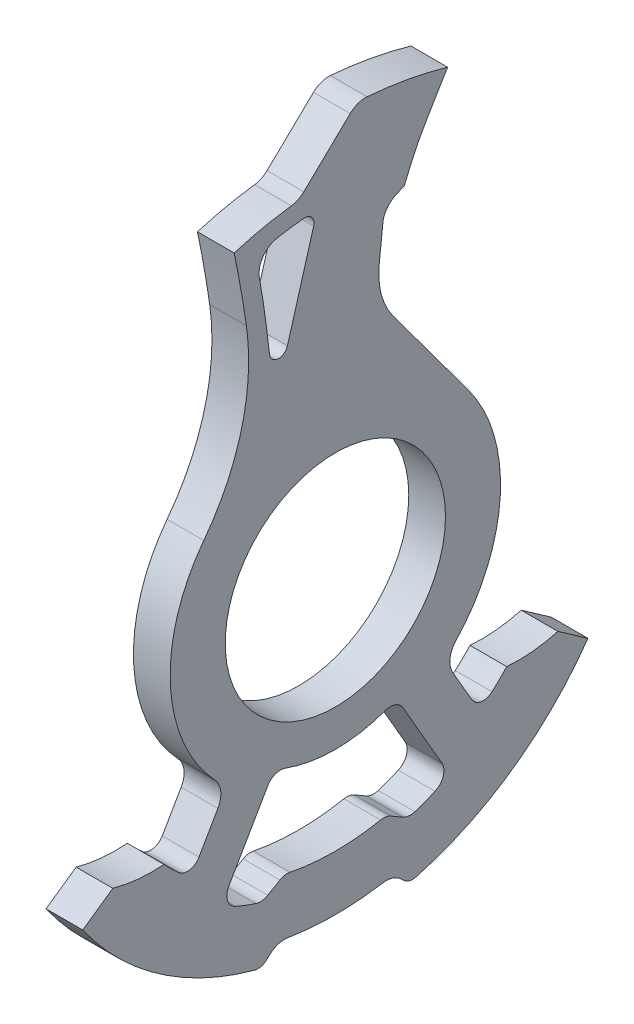
SolidWorks part; units mm, degrees
material "AR500"
ref_plane "Front Plane" through (0, 0, 0) normal (0, 0, 1) x (1, 0, 0)
ref_plane "Top Plane" through (0, 0, 0) normal (0, 1, 0) x (1, 0, 0)
ref_plane "Right Plane" through (0, 0, 0) normal (1, 0, 0) x (0, 0, -1)
other "Center of Mass"
sketch "Sketch1" plane through (0, 0, 0) normal (1, 0, 0) x (0, 0, -1)
  circle A0 centre (0, 0) radius 139.7 construction
  circle A1 centre (0, 0) radius 106.68 construction
  circle A2 centre (0, 0) radius 38.1 construction
  dimension "D1" = 279.4
  dimension "D2" = 33.02
  dimension "D3" = 76.2
sketch "Sketch2" plane through (0, 0, 0) normal (1, 0, 0) x (0, 0, -1)
  line L0 (0, 0) -> (38.858, 134.187) construction
  line L1 (38.858, 134.187) -> (32.2885, 123.3181)
  line L2 (0, 0) -> (0, 61.679) construction
  line L3 (7.5549, 139.4956) -> (-12.768, 119.9725)
  line L4 (-35.0051, 115.4602) -> (-40.3483, 140.8902) construction
  line L5 (23.88, 106.192) -> (20.1469, 96.5425) construction
  line L6 (23.88, 106.192) -> (16.9106, 103.1109)
  line L7 (16.9106, 103.1109) -> (15.1624, 86.8858)
  line L8 (-35.0051, 115.4602) -> (-4.6687, 124.6576) construction
  line L10 (0, -100.33) -> (0, 0) construction
  line L11 (-20.0866, -98.2987) -> (-25.4, -103.6121)
  line L16 (-49.9001, -64.1593) -> (-37.6706, -42.9773)
  line L17 (87.3871, -61.1891) -> (76.9839, -53.9047)
  line L18 (-87.3871, -61.1891) -> (-76.9839, -53.9047)
  line L19 (49.9001, -64.1593) -> (37.6706, -42.9773)
  line L24 (53.8815, -53.8815) -> (0, 0) construction
  line L25 (20.0866, -98.2987) -> (25.4, -103.6121)
  line L26 (19.9976, 69.057) -> (45.9419, 33.9922)
  circle A0 centre (0, 0) radius 139.7 construction
  arc A1 (38.858, 134.187) -> (7.5549, 139.4956) centre (0, 0) ccw
  arc A2 (-12.768, 119.9725) -> (-35.0051, 115.4602) centre (0, 0) ccw
  arc A3 (32.2885, 123.3181) -> (23.88, 106.192) centre (125.9607, 66.6999) ccw
  arc A4 (45.9419, 33.9922) -> (37.6706, -42.9773) centre (0, 0) cw
  circle A5 centre (0, 0) radius 38.1 construction
  arc A6 (19.9976, 69.057) -> (15.1624, 86.8858) centre (40.4162, 84.1646) cw
  arc A7 (-35.0051, 115.4602) -> (-30.7712, 91.5455) centre (-407.8633, 37.1165) cw
  arc A8 (-30.7712, 91.5455) -> (-45.5098, 34.5685) centre (-106.1896, 80.6597) cw
  arc A9 (-45.5098, 34.5685) -> (-37.6706, -42.9773) centre (0, 0) ccw
  arc A10 (-87.3871, -61.1891) -> (-25.4, -103.6121) centre (0, 0) ccw
  circle A11 centre (0, 0) radius 106.68 construction
  arc A18 (-76.9839, -53.9047) -> (-59.2852, -55.6031) centre (-63.357, -4.9665) ccw
  arc A19 (-59.2852, -55.6031) -> (-49.9001, -64.1593) centre (0, 0) ccw
  arc A20 (-20.0866, -98.2987) -> (20.0866, -98.2987) centre (0, 0) ccw
  arc A21 (59.2852, -55.6031) -> (49.9001, -64.1593) centre (0, 0) cw
  arc A22 (76.9839, -53.9047) -> (59.2852, -55.6031) centre (63.357, -4.9665) cw
  arc A23 (87.3871, -61.1891) -> (25.4, -103.6121) centre (0, 0) cw
  circle A24 centre (0, 0) radius 38.1
  dimension "D4" = 19.05
  dimension "D11" = 57.15
  dimension "D13" = 25.4
  dimension "D14" = 381
  dimension "D16" = 76.2
  dimension "D19" = 6.35
  dimension "D21" = 55
  dimension "D26" = 17.78
  dimension "D22" = 25.4
  dimension "D23" = 50.8
  dimension "D27" = 12.7
  dimension "D1" = 15
  dimension "D2" = 16.15
  dimension "D3" = 15
  dimension "D5" = 31.75
  dimension "D6" = 12.7
  dimension "D7" = 31.75
  dimension "D8" = 5
  dimension "D9" = 45
  dimension "D10" = 10
  dimension "D12" = 7.62
  dimension "D15" = 85
  dimension "D17" = 76.2
  dimension "D18" = 25.4
  dimension "D20" = 45
  dimension "D24" = 12.7
  dimension "D25" = 45
  dimension "D28" = 30
extrude "Boss-Extrude1" add sketch "Sketch2" along normal mid plane 12.7
sketch "Sketch3" plane through (6.35, 0, 0) normal (1, 0, 0) x (0, 0, -1)
  line L1 (-7.513, 109.7387) -> (-16.5762, 78.441)
  line L2 (15.1624, 86.8858) -> (16.9106, 103.1109) construction
  line L3 (-3.2803, 66.3447) -> (4.4504, 105.5668) construction
  line L4 (16.9106, 103.1109) -> (-8.0099, 108.0227) construction
  arc A0 (-12.768, 119.9725) -> (-35.0051, 115.4602) centre (0, 0) ccw construction
  arc A1 (-30.7712, 91.5455) -> (-35.0051, 115.4602) centre (-407.8633, 37.1165) ccw construction
  arc A2 (-7.513, 109.7387) -> (-10.8645, 113.7825) centre (-10.5627, 110.6219) ccw
  arc A3 (-12.768, 119.9725) -> (-35.0051, 115.4602) centre (0, 0) ccw construction
  arc A4 (-30.7712, 91.5455) -> (-35.0051, 115.4602) centre (-407.8633, 37.1165) ccw construction
  arc A5 (-10.8645, 113.7825) -> (-27.6085, 110.9156) centre (0, 0) ccw
  arc A6 (-22.7823, 78.981) -> (-27.6085, 110.9156) centre (-407.8633, 37.1165) ccw
  arc A7 (-24.4863, 92.4527) -> (-27.6085, 110.9156) centre (-407.8633, 37.1165) ccw construction
  arc A8 (-12.096, 113.6582) -> (-27.6085, 110.9156) centre (0, 0) ccw construction
  arc A14 (-22.7823, 78.981) -> (-16.5762, 78.441) centre (-19.6259, 79.3242) ccw
  point P18 (16.9106, 103.1109)
  dimension "D5" = 3.175
  dimension "D7" = 3.175
  dimension "D3" = 10
  dimension "D4" = 25.4
  dimension "D1" = 6.35
extrude "Cut-Extrude1" cut sketch "Sketch3" against normal through all
fillet "Fillet1" radius 7.62 8 edges at (0, 103.1109, -16.9106) (0, 110.9156, 27.6085) (0, 139.4956, -7.5549) (0, 119.9725, 12.768) (0, -42.9773, -37.6706) (0, -42.9773, 37.6706) (0, -98.2987, -20.0866) (0, -98.2987, 20.0866)
fillet "Fillet2" radius 4.572 4 edges at (0, -103.6121, 25.4) (0, -103.6121, -25.4) (0, -64.1593, -49.9001) (0, -64.1593, 49.9001)
sketch "Sketch4" plane through (6.35, 0, 0) normal (1, 0, 0) x (0, 0, -1)
  line L0 (-21.1843, -46.1721) -> (-39.646, -78.1487)
  line L1 (-40.6408, -48.1218) -> (-47.1846, -59.4559) construction
  line L2 (0, -81.28) -> (0, -50.8)
  line L3 (-25.3274, -83.8901) -> (-17.5035, -79.373)
  line L4 (-11.6185, -94.3061) -> (-25.8749, -102.5371) construction
  arc A0 (-39.646, -78.1487) -> (-25.3274, -83.8901) centre (0, 0) ccw
  arc A1 (0, -50.8) -> (-21.1843, -46.1721) centre (0, 0) cw
  circle A2 centre (0, 0) radius 38.1 construction
  circle A3 centre (0, 0) radius 106.68 construction
  arc A4 (-17.5035, -79.373) -> (0, -81.28) centre (0, 0) ccw
  arc A5 (-16.2916, -98.9984) -> (16.2916, -98.9984) centre (0, 0) ccw construction
  arc A6 (-87.3871, -61.1891) -> (-27.9851, -102.9439) centre (0, 0) ccw construction
  arc A7 (-16.2916, -98.9984) -> (-22.9171, -101.1292) centre (-17.5289, -106.5173) ccw construction
  dimension "D1" = 50.8
  dimension "D3" = 19.05
  dimension "D4" = 19.05
  dimension "D2" = 15.875
  dimension "D5" = 30
  dimension "D6" = 15.875
extrude "Cut-Extrude2" cut sketch "Sketch4" against normal through all
mirror "Mirror1" about plane through (-6.35, -81.28, 0) normal (0, 0, -1) of "Cut-Extrude2"
fillet "Fillet3" radius 5.08 8 edges at (0, -78.1487, -39.646) (0, -83.8901, -25.3274) (0, -79.373, -17.5035) (0, -79.373, 17.5035) (0, -83.8901, 25.3274) (0, -46.1721, 21.1843) (0, -46.1721, -21.1843) (0, -78.1487, 39.646)
